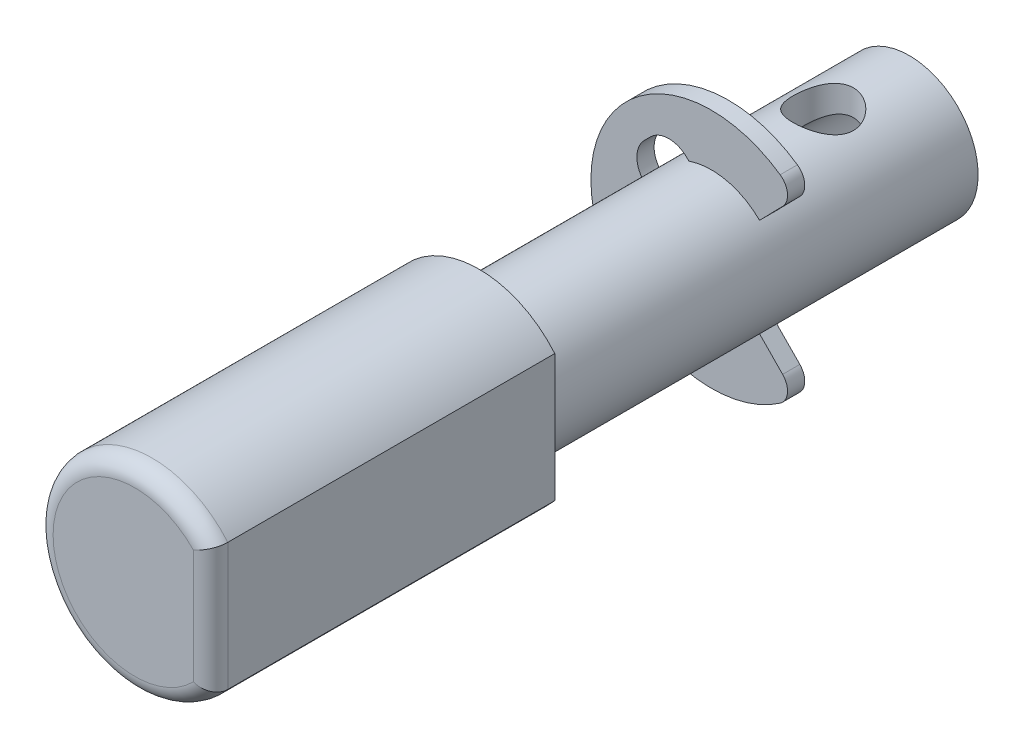
SolidWorks part; units mm, degrees
ref_plane "Спереди" through (0, 0, 0) normal (0, 0, 1) x (1, 0, 0)
ref_plane "Сверху" through (0, 0, 0) normal (0, 1, 0) x (1, 0, 0)
ref_plane "Справа" through (0, 0, 0) normal (1, 0, 0) x (0, 0, -1)
sketch "Эскиз1" plane through (0, 0, 0) normal (0, 0, 1) x (1, 0, 0)
  line L0 (2.2, -1.8508) -> (2.2, 1.8508)
  arc A1 (2.2, 1.8508) -> (2.2, -1.8508) centre (0, 0) ccw
extrude "Бобышка-Вытянуть1" add sketch "Эскиз1" along normal blind 10
fillet "Скругление1" radius 0.5 2 edges at (2.2, 0, 10) (-2.875, 0, 10)
sketch "Эскиз2" plane through (0, 0, 0) normal (0, 0, -1) x (-1, 0, 0)
  circle A0 centre (0, 0) radius 2
  dimension "D1" = 4
extrude "Бобышка-Вытянуть2" add sketch "Эскиз2" along normal blind 12.5
ref_plane "Плоскость1" through (0, 0, -7.25) normal (0, 0, 1) x (1, 0, 0)
sketch "Эскиз3" plane through (0, 0, -7.25) normal (0, 0, 1) x (1, 0, 0)
  line L1 (2.4495, -2.5) -> (1.3997, -1.4286)
  line L2 (2.4495, 2.5) -> (1.3997, 1.4286)
  arc A0 (1.3997, 1.4286) -> (1.3997, -1.4286) centre (0, 0) ccw
  arc A1 (2.4495, 2.5) -> (2.4495, -2.5) centre (0, 0) ccw
  dimension "D1" = 4
  dimension "D2" = 7
extrude "Бобышка-Вытянуть3" add sketch "Эскиз3" along normal blind 0.5
sketch "Эскиз4" plane through (0, 0, -7.25) normal (0, 0, -1) x (-1, 0, 0)
  line L1 (1.9445, -1.7678) -> (1.7678, -1.9445)
  line L2 (1.7678, 1.9445) -> (1.9445, 1.7678)
  line L4 (0.7071, -1.9445) -> (0.653, -1.8904)
  line L5 (1.9445, -0.7071) -> (1.8904, -0.653)
  line L6 (0.7071, 1.9445) -> (0.653, 1.8904)
  line L7 (1.9445, 0.7071) -> (1.8904, 0.653)
  arc A3 (1.8904, 0.653) -> (0.653, 1.8904) centre (0, 0) ccw
  arc A4 (0.653, -1.8904) -> (1.8904, -0.653) centre (0, 0) ccw
  arc A5 (1.7678, -1.9445) -> (0.7071, -1.9445) centre (1.2374, -1.4142) cw
  arc A6 (1.9445, -1.7678) -> (1.9445, -0.7071) centre (1.4142, -1.2374) ccw
  arc A7 (1.9445, 1.7678) -> (1.9445, 0.7071) centre (1.4142, 1.2374) cw
  arc A8 (1.7678, 1.9445) -> (0.7071, 1.9445) centre (1.2374, 1.4142) ccw
  dimension "D1" = 0.75
extrude "Вырез-Вытянуть1" cut sketch "Эскиз4" against normal blind 0.5
fillet "Скругление2" radius 0.5 2 edges at (2.4495, -2.5, -7) (2.4495, 2.5, -7)
hole_wizard "Отверстие обработанное метчиком M31" positions "Эскиз5" profile "Эскиз7" tap size "M3" standard "ISO"
sketch "Эскиз5" plane through (0, 0, -12.5) normal (0, 0, -1) x (-1, 0, 0)
  point P0 (0, 0)
sketch "Эскиз7" plane through (0, 0, -12.5) normal (1, 0, 0) x (0, 1, 0)
  line L0 (0, 0) -> (0, 9.2511)
  line L1 (0, 9.2511) -> (1.25, 8.5)
  line L2 (1.25, 8.5) -> (1.25, 0)
  line L5 (1.25, 0) -> (0, 0)
  line L10 (0, 9.2511) -> (-1.25, 8.5) construction
  line L11 (0, -6.35) -> (0, 107.95) construction
  dimension "Диаметр сверла" = 2.5
  dimension "Глубина сверла" = 8.5
  dimension "Угол заточки сверла" = 118
sketch "Эскиз8" plane through (0, 0, 0) normal (0, 1, 0) x (1, 0, 0)
  line L0 (2, 12.5) -> (-2, 12.5) construction
  circle A0 centre (0, 10) radius 0.875
  dimension "D1" = 1.75
  dimension "D2" = 2.5
extrude "Вырез-Вытянуть2" cut sketch "Эскиз8" against normal blind 10 and the other way blind 10
